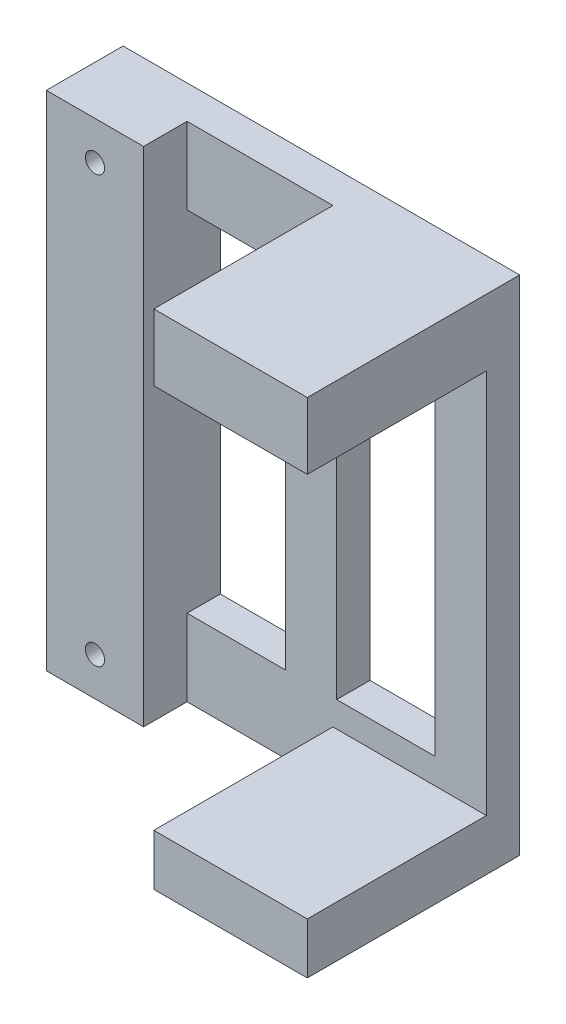
SolidWorks part; units mm, degrees
ref_plane "前视基准面" through (0, 0, 0) normal (0, 0, 1) x (1, 0, 0)
ref_plane "上视基准面" through (0, 0, 0) normal (0, 1, 0) x (1, 0, 0)
ref_plane "右视基准面" through (0, 0, 0) normal (1, 0, 0) x (0, 0, -1)
sketch "草图2" plane through (0, 0, 0) normal (0, 0, 1) x (1, 0, 0)
  line L3 (-8.65, -9.825) -> (6.85, -9.825)
  line L4 (6.85, 9.825) -> (6.85, -9.825)
  line L5 (0, 0) -> (2.4933, 0) construction
  line L6 (0, 0) -> (0, -3.9686) construction
  line L15 (-8.65, 9.825) -> (6.85, 9.825)
  line L16 (-4.85, 6.825) -> (-1, 6.825)
  line L17 (-4.85, 6.825) -> (-4.85, -6.825)
  line L18 (-4.85, -6.825) -> (-1, -6.825)
  line L20 (-8.65, 9.825) -> (-8.65, -9.825)
  line L21 (1, 6.825) -> (4.85, 6.825)
  line L23 (1, -6.825) -> (1, 6.825)
  line L25 (-1, -6.825) -> (-1, 6.825)
  line L26 (4.85, 6.825) -> (4.85, -6.825)
  line L28 (1, -6.825) -> (4.85, -6.825)
  point P0 (0, 0)
  dimension "D1" = 15.5
  dimension "D3" = 19.65
  dimension "D4" = 3.8
  dimension "D5" = 3
  dimension "D6" = 2
  dimension "D8" = 3
  dimension "D9" = 2
extrude "凸台-拉伸1" add sketch "草图2" along normal blind 1.3
sketch "草图3" plane through (0, 0, 1.3) normal (0, 0, 1) x (1, 0, 0)
  line L1 (0.85, 9.825) -> (6.85, 9.825)
  line L2 (0.85, 9.825) -> (0.85, 7.225)
  line L3 (0.85, 7.225) -> (6.85, 7.225)
  line L4 (6.85, 9.825) -> (6.85, 7.225)
  line L5 (6.85, -9.825) -> (6.85, 9.825) construction
  line L6 (0.85, -7.825) -> (6.85, -7.825)
  line L8 (0.85, -9.825) -> (6.85, -9.825)
  line L9 (6.85, -7.825) -> (6.85, -9.825)
  line L10 (-8.65, -9.825) -> (6.85, -9.825) construction
  line L11 (0.85, -7.825) -> (0.85, -9.825)
  line L12 (6.85, 9.825) -> (-8.65, 9.825) construction
  dimension "D1" = 2
  dimension "D2" = 2.6
  dimension "D3" = 6
  dimension "D4" = 6
extrude "凸台-拉伸2" add sketch "草图3" along normal blind 7
sketch "草图10" plane through (0, 0, 1.3) normal (0, 0, 1) x (1, 0, 0)
  line L0 (-8.65, 9.825) -> (-8.65, -9.825) construction
  line L1 (-8.65, 9.825) -> (-4.85, 9.825)
  line L2 (-8.65, 9.825) -> (-8.65, -9.825)
  line L3 (-8.65, -9.825) -> (-4.85, -9.825)
  line L4 (-4.85, 9.825) -> (-4.85, -9.825)
  line L5 (0.85, 9.825) -> (-8.65, 9.825) construction
  line L6 (-8.65, -9.825) -> (0.85, -9.825) construction
  line L7 (-4.85, 6.825) -> (-4.85, -6.825) construction
extrude "凸台-拉伸4" add sketch "草图10" along normal blind 1.7
sketch "草图9" plane through (0, 0, 1.3) normal (0, 0, 1) x (1, 0, 0)
  line L0 (0.85, 9.825) -> (-4.85, 9.825) construction
  line L1 (-8.65, 9.825) -> (-8.65, -9.825) construction
  line L2 (-4.85, -9.825) -> (0.85, -9.825) construction
  circle A0 centre (-6.75, 8.325) radius 0.375
  circle A1 centre (-6.75, -8.325) radius 0.375
  dimension "D1" = 0.75
  dimension "D2" = 0.75
  dimension "D3" = 1.5
  dimension "D4" = 1.9
  dimension "D5" = 1.5
  dimension "D6" = 1.9
extrude "切除-拉伸2" cut sketch "草图9" against normal up to next from surface starting at face at (-6.75, 0, 3)
